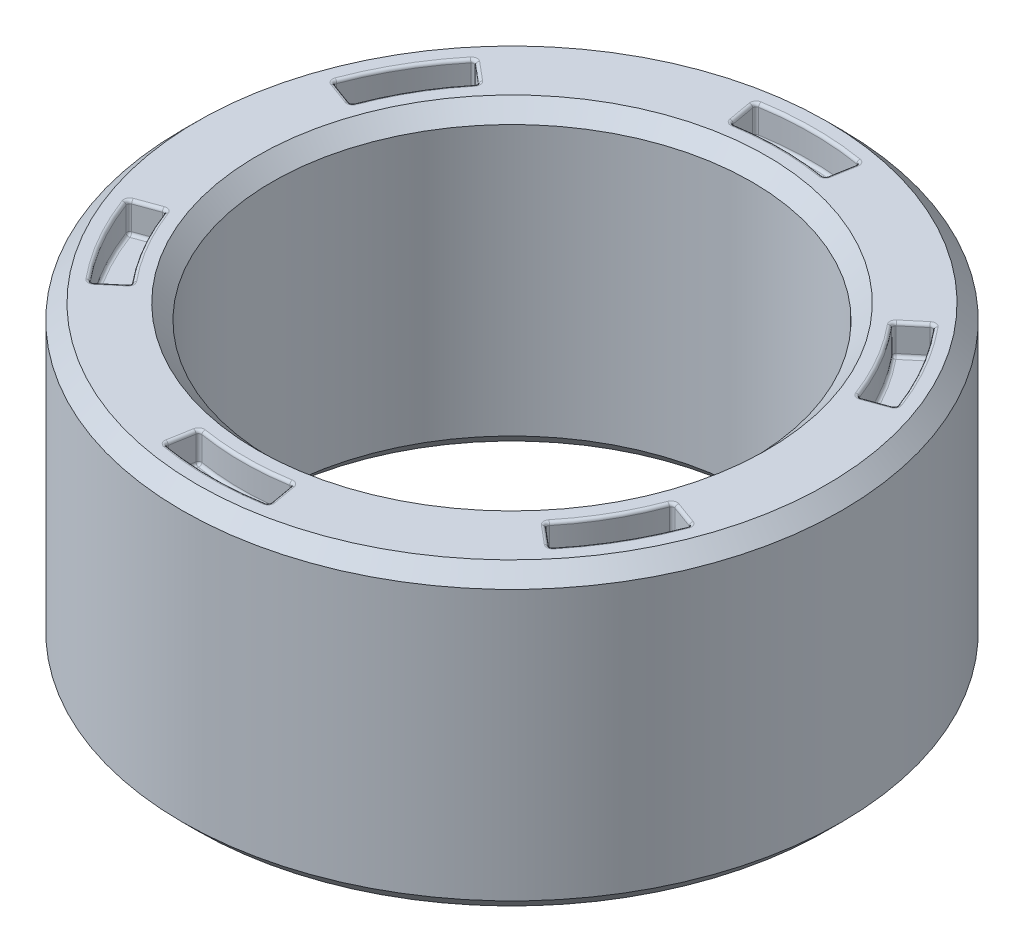
SolidWorks part; units mm, degrees
ref_plane "Front Plane" through (0, 0, 0) normal (0, 0, 1) x (1, 0, 0)
ref_plane "Top Plane" through (0, 0, 0) normal (0, 1, 0) x (1, 0, 0)
ref_plane "Right Plane" through (0, 0, 0) normal (1, 0, 0) x (0, 0, -1)
sketch "Sketch1" plane through (0, 0, 0) normal (0, 1, 0) x (1, 0, 0)
  circle A0 centre (0, 0) radius 11
  circle A1 centre (0, 0) radius 8
  dimension "D1" = 22
  dimension "D2" = 16
extrude "Boss-Extrude1" add sketch "Sketch1" along normal blind 10
chamfer "Chamfer1" distance 0.5 angle 45 4 edges at (0, 0, 8) (0, 0, 11) (0, 10, 11) (0, 10, 8)
sketch "Sketch2" plane through (0, 10, 0) normal (0, 1, 0) x (1, 0, 0)
  line L0 (0, 0) -> (0, 9) construction
  line L1 (0, 0) -> (1.5628, 8.8633) construction
  line L2 (0, 0) -> (-1.5628, 8.8633) construction
  line L3 (-1.5628, 8.8633) -> (-1.7365, 9.8481)
  line L4 (1.5628, 8.8633) -> (1.7365, 9.8481)
  circle A0 centre (0, 0) radius 9 construction
  circle A1 centre (0, 0) radius 10 construction
  arc A2 (1.5628, 8.8633) -> (-1.5628, 8.8633) centre (0, 0) ccw
  arc A3 (1.7365, 9.8481) -> (-1.7365, 9.8481) centre (0, 0) ccw
  dimension "D1" = 18
  dimension "D2" = 20
  dimension "D3" = 10
extrude "Cut-Extrude1" cut sketch "Sketch2" against normal blind 1
fillet "Fillet1" radius 0.1 12 edges at (1.5628, 9.5, -8.8633) (1.7365, 9.5, -9.8481) (1.6497, 10, -9.3557) (1.6497, 9, -9.3557) (-1.7365, 9.5, -9.8481) (-1.5628, 9.5, -8.8633) (-1.6497, 10, -9.3557) (-1.6497, 9, -9.3557) (0, 10, -9) (0, 9, -9) (0, 10, -10) (0, 9, -10)
pattern_circular "CirPattern1" count 6 over 360 about axis through (0, 10, 0) along (0, -1, 0) of "Cut-Extrude1", "Fillet1"
